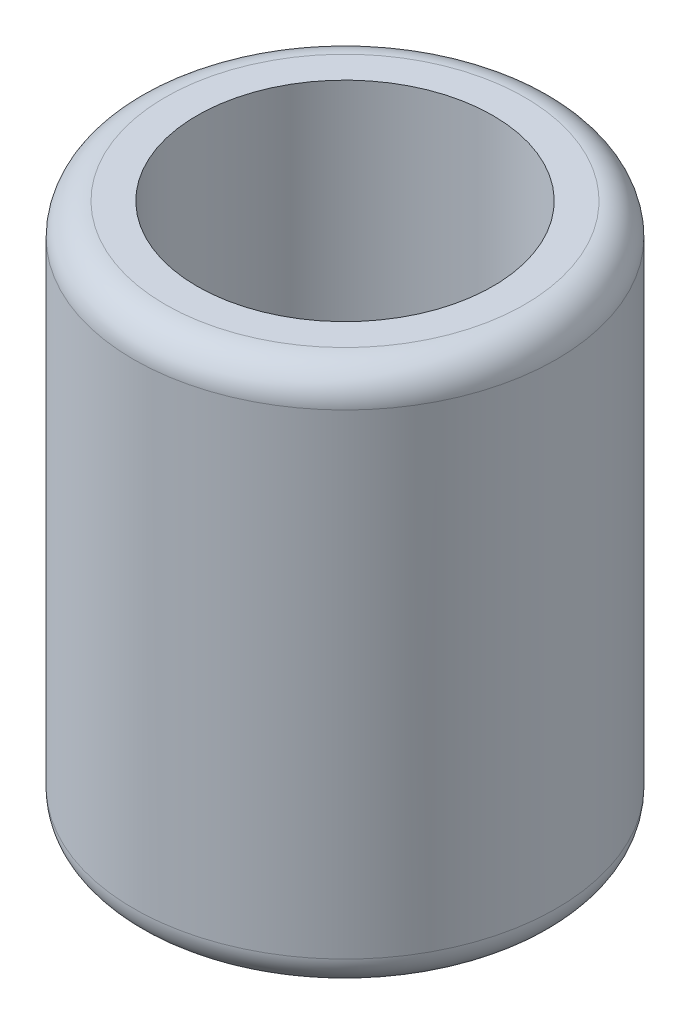
SolidWorks part; units mm, degrees
note: The reader was unsure of these and kept them because the rebuilt part matched: shared geometry of "草图1<3>".
ref_plane "前视基准面" through (0, 0, 0) normal (0, 0, 1) x (1, 0, 0)
ref_plane "上视基准面" through (0, 0, 0) normal (0, 1, 0) x (1, 0, 0)
ref_plane "右视基准面" through (0, 0, 0) normal (1, 0, 0) x (0, 0, -1)
sketch "草图1" plane through (0, 0, 0) normal (0, 1, 0) x (1, 0, 0)
  circle A0 centre (0, 0) radius 20
  circle A1 centre (0, 0) radius 14
  circle A2 centre (0, 0) radius 8.1
  circle A4 centre (0, 0) radius 11
  dimension "D1" = 28
  dimension "D2" = 40
  dimension "D3" = 16.2
  dimension "D4" = 22
extrude "凸台-拉伸1" add sketch "草图1" along normal blind 11 contours A4 A2
sketch "草图4" plane through (0, 11, 0) normal (0, 1, 0) x (1, 0, 0)
  circle A0 centre (0, 0) radius 8.1
curve "螺旋线/涡状线1" pitch 2 height 11 radius 8.1 centre (0, 11, 0) axis (0, -1, 0) start towards (0, 0, 1)
ref_plane "基准面5" through (0, 0, 0) normal (0.7071, 0, -0.7071) x (-0.7071, 0, -0.7071)
sketch "草图7" plane through (0, 0, 0) normal (0.7071, 0, -0.7071) x (-0.7071, 0, -0.7071)
  line L0 (8.1, 10.65) -> (8.1, 11.35)
  line L1 (11, 11) -> (-11, 11) construction
  line L2 (8.1, 11.35) -> (7.6, 11)
  line L3 (8.1, 11) -> (-8.1, 11) construction
  line L4 (8.1, 11) -> (7.6, 11) construction
  line L5 (8.1, 10.65) -> (7.6, 11)
  spline S0 degree 3 poles (8.1, 11) (8.1, 10.9586) (7.6782, 10.8749) (5.8767, 10.75) (3.1804, 10.625) (0, 10.5) (-3.1804, 10.375) (-5.8767, 10.25) (-7.6782, 10.125) (-8.3109, 10) (-7.6782, 9.875) (-5.8767, 9.75) (-2.2817, 9.5833) (2.2817, 9.4167) (5.8767, 9.25) (7.6782, 9.125) (8.3109, 9) (7.6782, 8.875) (5.8767, 8.75) (2.2817, 8.5833) (-2.2817, 8.4167) (-5.8767, 8.25) (-7.6782, 8.125) (-8.3109, 8) (-7.6782, 7.875) (-5.8767, 7.75) (-2.2817, 7.5833) (2.2817, 7.4167) (5.8767, 7.25) (7.6782, 7.125) (8.3109, 7) (7.6782, 6.875) (5.8767, 6.75) (2.2817, 6.5833) (-2.2817, 6.4167) (-5.8767, 6.25) (-7.6782, 6.125) (-8.3109, 6) (-7.6782, 5.875) (-5.8767, 5.75) (-2.2817, 5.5833) (2.2817, 5.4167) (5.8767, 5.25) (7.6782, 5.125) (8.3109, 5) (7.6782, 4.875) (5.8767, 4.75) (2.2817, 4.5833) (-2.2817, 4.4167) (-5.8767, 4.25) (-7.6782, 4.125) (-8.3109, 4) (-7.6782, 3.875) (-5.8767, 3.75) (-2.2817, 3.5833) (2.2817, 3.4167) (5.8767, 3.25) (7.6782, 3.125) (8.3109, 3) (7.6782, 2.875) (5.8767, 2.75) (2.2817, 2.5833) (-2.2817, 2.4167) (-5.8767, 2.25) (-7.6782, 2.125) (-8.3109, 2) (-7.6782, 1.875) (-5.8767, 1.75) (-2.2817, 1.5833) (2.2817, 1.4167) (5.8767, 1.25) (7.6782, 1.125) (8.3109, 1) (7.6782, 0.875) (5.8767, 0.75) (3.1804, 0.625) (0, 0.5) (-3.1804, 0.375) (-5.8767, 0.25) (-7.6782, 0.1251) (-8.1, 0.0414) (-8.1, 0) knots 0 0 0 0 0.011364 0.022727 0.034091 0.045455 0.056818 0.068182 0.079545 0.090909 0.102273 0.113636 0.125 0.147727 0.159091 0.170455 0.181818 0.193182 0.204545 0.215909 0.238636 0.25 0.261364 0.272727 0.284091 0.295455 0.306818 0.329545 0.340909 0.352273 0.363636 0.375 0.386364 0.397727 0.420455 0.431818 0.443182 0.454545 0.465909 0.477273 0.488636 0.511364 0.522727 0.534091 0.545455 0.556818 0.568182 0.579545 0.602273 0.613636 0.625 0.636364 0.647727 0.659091 0.670455 0.693182 0.704545 0.715909 0.727273 0.738636 0.75 0.761364 0.784091 0.795455 0.806818 0.818182 0.829545 0.840909 0.852273 0.875 0.886364 0.897727 0.909091 0.920455 0.931818 0.943182 0.954545 0.965909 0.977273 0.988636 1 1 1 1 construction
  dimension "D1" = 0.5
  dimension "D2" = 0.7
sweep "扫描2" add profiles "草图7" path "螺旋线/涡状线1"
sketch "草图8" plane through (0, 0, 0) normal (0.7071, 0, -0.7071) x (-0.7071, 0, -0.7071)
  line L1 (11, 11) -> (-9.9656, 11)
  line L2 (11, 11) -> (11, 14.3472)
  line L3 (11, 14.3472) -> (-9.9656, 14.3472)
  line L4 (-9.9656, 11) -> (-9.9656, 14.3472)
extrude "切除-拉伸1" cut sketch "草图8" against normal through all both and the other way through all
sketch "草图9" plane through (0, 11, 0) normal (0, 1, 0) x (1, 0, 0)
  line L0 (0, 0) -> (-5.7276, 5.7276) construction
  line L1 (4.2993, -4.2993) -> (-4.2993, 4.2993) construction
  line L2 (-5.7276, 5.7276) -> (-4.0907, 6.3491)
  line L3 (-4.0907, 6.3491) -> (-5.0014, 5.0014)
  line L4 (-5.0014, 5.0014) -> (-5.7276, 5.7276)
  circle A0 centre (0, 0) radius 8.1
extrude "切除-拉伸2" cut sketch "草图9" against normal blind 1
extrude "凸台-拉伸2" add sketch "草图1<3>" along normal blind 31 contours A0 A1
sketch "草图1<3>" plane through (0, 0, 0) normal (0, 1, 0) x (1, 0, 0) same geometry as "草图1"
sketch "草图2" plane through (0, 0, 0) normal (0, -1, 0) x (1, 0, 0)
  circle A1 centre (0, 0) radius 20
  circle A2 centre (0, 0) radius 20
  dimension "D1" = 0
extrude "凸台-拉伸4" add sketch "草图2" along normal blind 20
fillet "圆角1" radius 3 2 edges at (0, -20, -20) (0, 31, 20)
